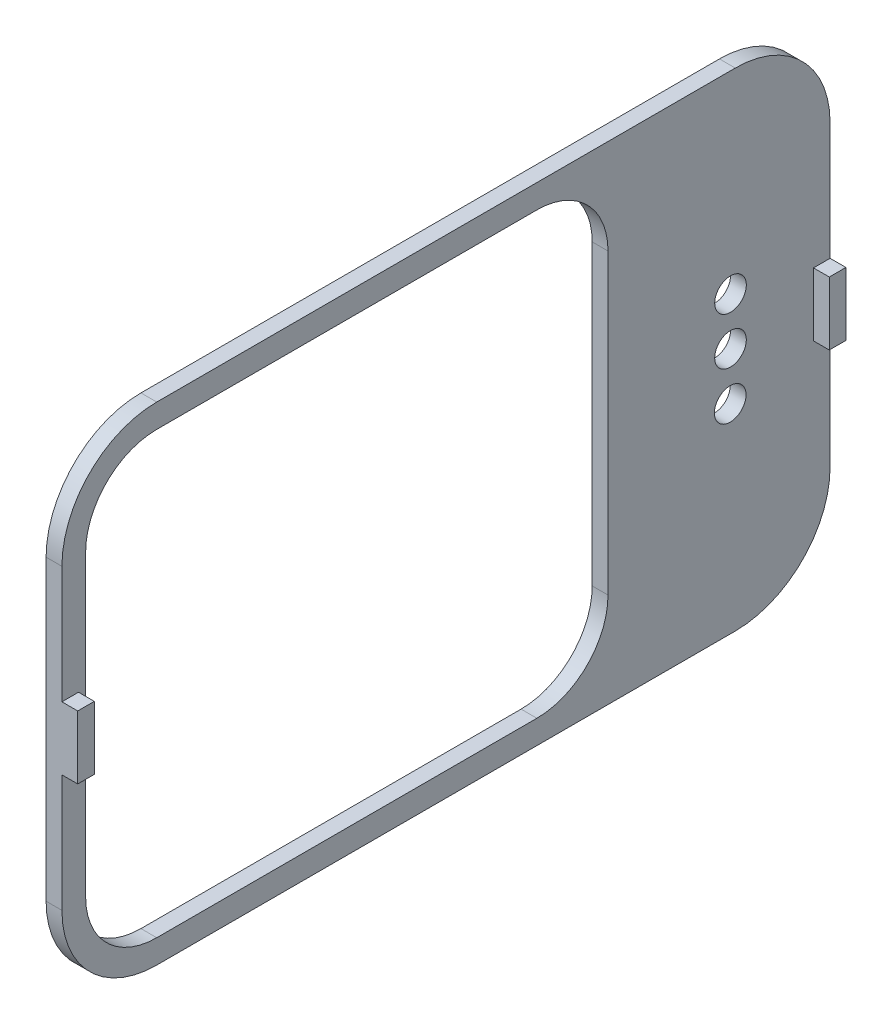
SolidWorks part; units mm, degrees
ref_plane "前视基准面" through (0, 0, 0) normal (0, 0, 1) x (1, 0, 0)
ref_plane "上视基准面" through (0, 0, 0) normal (0, 1, 0) x (1, 0, 0)
ref_plane "右视基准面" through (0, 0, 0) normal (1, 0, 0) x (0, 0, -1)
other "Configuration Table"
sketch "草图1" plane through (0, 0, 0) normal (1, 0, 0) x (0, 0, -1)
  line L16 (26.8102, -0.1143) -> (26.8102, 18.7357)
  line L17 (-15.7898, -6.1143) -> (20.8102, -6.1143)
  line L18 (-21.7898, 18.7357) -> (-21.7898, -0.1143)
  line L19 (20.8102, 24.7357) -> (-15.7898, 24.7357)
  arc A12 (20.8102, -6.1143) -> (26.8102, -0.1143) centre (20.8102, -0.1143) ccw
  arc A13 (-21.7898, -0.1143) -> (-15.7898, -6.1143) centre (-15.7898, -0.1143) ccw
  arc A14 (-15.7898, 24.7357) -> (-21.7898, 18.7357) centre (-15.7898, 18.7357) ccw
  arc A15 (26.8102, 18.7357) -> (20.8102, 24.7357) centre (20.8102, 18.7357) ccw
  point P0 (0, 0)
  dimension "D2" = 6
  dimension "D1" = 30.85
  dimension "D3" = 48.6
extrude "凸台-拉伸1" add sketch "草图1" along normal blind 1
sketch "草图2" plane through (0, 0, 0) normal (-1, 0, 0) x (0, 0, 1)
  line L2 (15.7898, -6.1143) -> (-20.8102, -6.1143) construction
  line L7 (21.7898, 18.7357) -> (21.7898, -0.1143) construction
  line L8 (-20.8102, 24.7357) -> (15.7898, 24.7357) construction
  line L12 (-12.7598, 18.7357) -> (-12.7598, -0.1143)
  line L13 (15.7898, 23.2357) -> (-8.2598, 23.2357)
  line L15 (-8.2598, -4.6143) -> (15.7898, -4.6143)
  line L126 (20.2898, 18.7357) -> (20.2898, -0.1143)
  arc A0 (15.7898, -4.6143) -> (20.2898, -0.1143) centre (15.7898, -0.1143) ccw
  arc A1 (-12.7598, -0.1143) -> (-8.2598, -4.6143) centre (-8.2598, -0.1143) ccw
  arc A2 (15.7898, 23.2357) -> (20.2898, 18.7357) centre (15.7898, 18.7357) cw
  arc A3 (-12.7598, 18.7357) -> (-8.2598, 23.2357) centre (-8.2598, 18.7357) cw
  point P0 (-12.2873, -4.7475)
  dimension "D2" = 1.5
  dimension "D1" = 4.5
  dimension "D3" = 1.5
  dimension "D4" = 1.5
extrude "切除-拉伸1" cut sketch "草图2" against normal through all
sketch "草图3" plane through (0, 0, 0) normal (-1, 0, 0) x (0, 0, 1)
  line L0 (-27.1453, 9.5025) -> (-34.4305, 9.5025) construction
  circle A1 centre (-20.4913, 6.4943) radius 1
  circle A3 centre (-20.5098, 9.5025) radius 1
  circle A4 centre (-20.4913, 6.4943) radius 1
  circle A5 centre (-20.5098, 12.5025) radius 1
  circle A6 centre (-20.5098, 9.5025) radius 1
  circle A7 centre (-20.5098, 12.5025) radius 1
extrude "切除-拉伸2" cut sketch "草图3" against normal through all contours A3 | A5 | A1
sketch "草图4" plane through (1, 0, 0) normal (1, 0, 0) x (0, 0, -1)
  line L1 (-20.7398, 7.3107) -> (-21.7898, 7.3107)
  line L2 (-20.7398, 7.3107) -> (-20.7398, 11.3107)
  line L3 (-20.7398, 11.3107) -> (-21.7898, 11.3107)
  line L4 (-21.7898, 7.3107) -> (-21.7898, 11.3107)
  line L5 (-21.7898, 18.7357) -> (-21.7898, -0.1143) construction
  line L6 (26.8102, -0.1143) -> (26.8102, 18.7357) construction
  line L7 (26.8102, 7.3107) -> (25.7602, 7.3107)
  line L8 (26.8102, 7.3107) -> (26.8102, 11.3107)
  line L9 (26.8102, 11.3107) -> (25.7602, 11.3107)
  line L10 (25.7602, 7.3107) -> (25.7602, 11.3107)
  line L11 (-21.7898, 18.7357) -> (-21.7898, -0.1143) construction
  point P16 (-21.7898, 9.3107)
  point P17 (-21.7898, 9.3107)
  point P18 (25.7602, 9.3107)
  dimension "D1" = 4
  dimension "D2" = 1.05
extrude "凸台-拉伸2" add sketch "草图4" along normal blind 1
